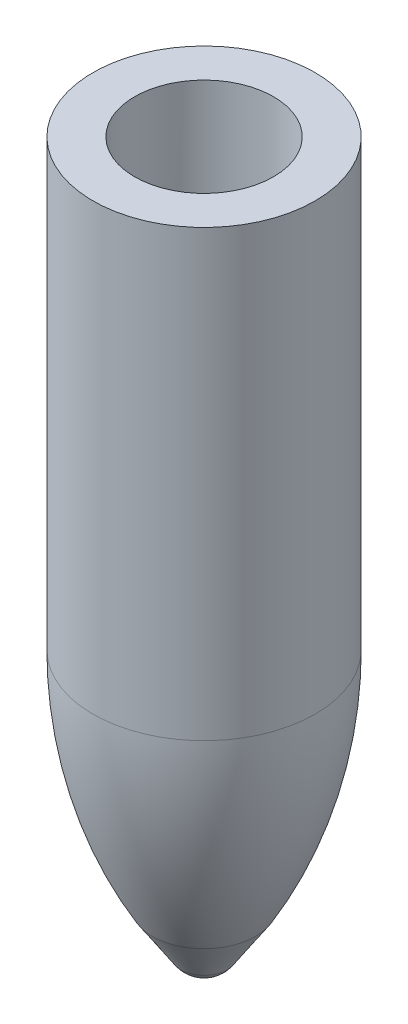
SolidWorks part; units mm, degrees
ref_plane "Front" through (0, 0, 0) normal (0, 0, 1) x (1, 0, 0)
ref_plane "Top" through (0, 0, 0) normal (0, 1, 0) x (1, 0, 0)
ref_plane "Right" through (0, 0, 0) normal (1, 0, 0) x (0, 0, -1)
ref_axis "Center Axis" through (0, 0, -13.97) along (0, 0, 1)
sketch "Sketch1" plane through (0, 0, 0) normal (0, 0, 1) x (1, 0, 0)
  line L0 (0, 0) -> (0, -50.8)
  line L1 (12.7, -84.401) -> (12.7, 0)
  line L2 (12.7, 0) -> (0, 0)
  arc A0 (0, -50.8) -> (12.7, -84.401) centre (50.8, -50.8) ccw
  dimension "D4" = 50.8
  dimension "D1" = 12.7
  dimension "D3" = 50.8
revolve "Revolve1" add sketch "Sketch1" angle 360 about L1
shell "Shell2" thickness 4.7625 removed face at (25.4, 0, 0)
sketch "Sketch2" plane through (0, 0, 0) normal (0, 0, 1) x (1, 0, 0)
  line L0 (25.4, -50.8) -> (0, -50.8) construction
  line L1 (12.7, -50.8) -> (0, -50.8)
  line L4 (10.0472, -81.129) -> (6.8059, -76.2)
  line L5 (12.7, -82.5595) -> (12.7, -50.8)
  arc A1 (0, -50.8) -> (12.7, -84.401) centre (50.8, -50.8) ccw construction
  arc A3 (0, -50.8) -> (10.0472, -81.129) centre (50.8, -50.8) ccw
  arc A4 (12.7, -82.5595) -> (10.0472, -81.129) centre (12.7, -79.3845) cw
  dimension "D2" = 3.175
sketch "Sketch3" plane through (0, 0, 0) normal (0, 0, 1) x (1, 0, 0)
  line L1 (0, -50.8) -> (27.1811, -50.8)
  line L2 (0, -50.8) -> (0, -89.2545)
  line L3 (0, -89.2545) -> (27.1811, -89.2545)
  line L4 (27.1811, -50.8) -> (27.1811, -89.2545)
extrude "Cut-Extrude1" cut sketch "Sketch3" against normal through all both and the other way through all
revolve "Revolve3" add sketch "Sketch2" angle 360 about L5 region at (7.5329, -63.5037, 0)
